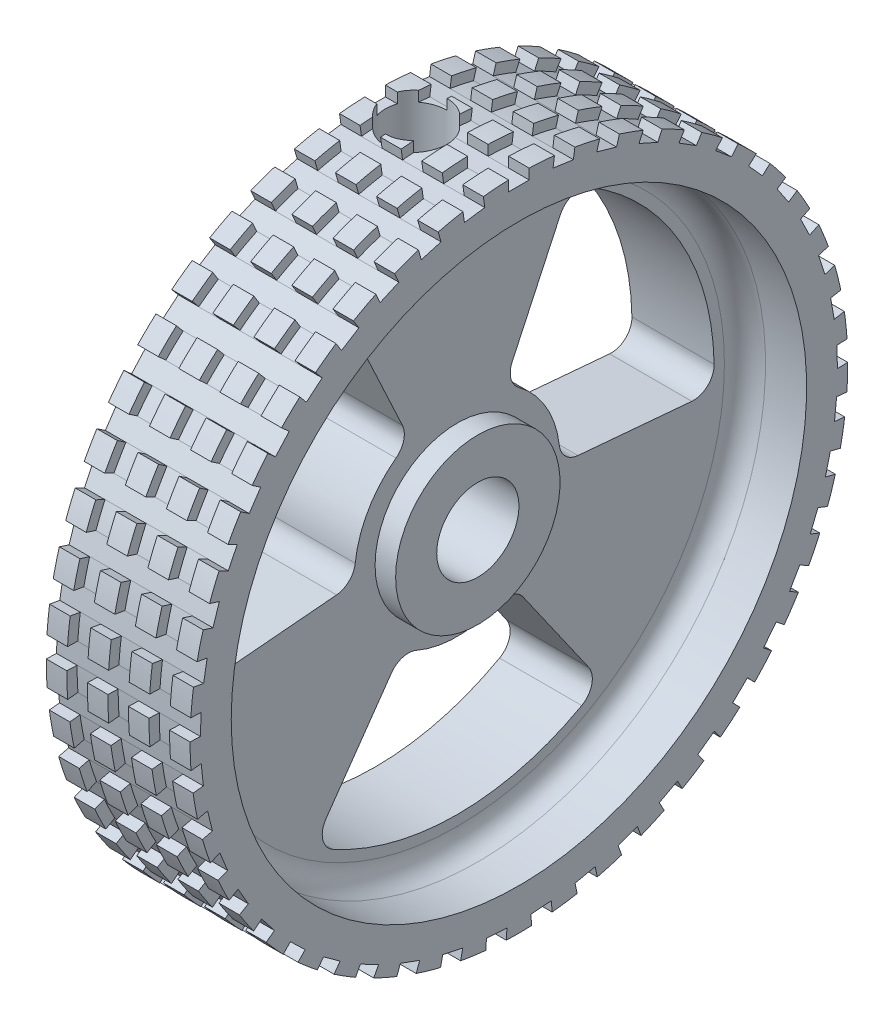
SolidWorks part; units mm, degrees
ref_plane "Front" through (0, 0, 0) normal (0, 0, 1) x (1, 0, 0)
ref_plane "Top" through (0, 0, 0) normal (0, 1, 0) x (1, 0, 0)
ref_plane "Right" through (0, 0, 0) normal (1, 0, 0) x (0, 0, -1)
sketch "Sketch1" plane through (0, 0, 0) normal (0, 0, 1) x (1, 0, 0)
  line L0 (0, 0) -> (0, 24.7296) construction
  line L1 (0, 0) -> (11.8667, 0) construction
  line L2 (0, 2) -> (5, 2)
  line L3 (5, 2) -> (5, 4)
  line L4 (5, 4) -> (4, 4)
  line L5 (4, 4) -> (4, 14)
  line L6 (4, 14) -> (7, 14)
  line L7 (7, 14) -> (7, 16)
  line L8 (7, 16) -> (0, 16)
  line L9 (0, 16) -> (0, 2)
  dimension "D1" = 4
  dimension "D2" = 32
  dimension "D3" = 8
  dimension "D4" = 28
  dimension "D5" = 4
  dimension "D6" = 7
  dimension "D7" = 5
revolve "Revolve1" add sketch "Sketch1" angle 360 about L1
sketch "Sketch2" plane through (0, 0, 0) normal (0, 0, 1) x (1, 0, 0)
  line L0 (2, 0) -> (2, 15.8033) construction
  line L2 (2, 16) -> (3.5, 16)
  line L3 (7, 16) -> (0, 16) construction
  line L4 (3.5, 16) -> (3.5, 11.5)
  line L6 (3.5, 11.5) -> (2.9, 11.5)
  line L7 (2.9, 11.5) -> (2.9, 0)
  line L8 (0, 0) -> (6.9041, 0) construction
  line L9 (2, 0) -> (2, 16)
  line L10 (0, 16) -> (0, -16) construction
  line L11 (2, 0) -> (2.9, 0)
  dimension "D1" = 3
  dimension "D2" = 1.8
  dimension "D3" = 2
  dimension "D4" = 4.5
revolve "Cut-Revolve3" cut sketch "Sketch2" angle 360 about L0
sketch "Sketch3" plane through (4, 0, 0) normal (1, 0, 0) x (0, 0, -1)
  line L0 (-2.6967, -4.2104) -> (-7, -10.3562)
  line L1 (2.6967, -4.2104) -> (7, -10.3562)
  line L3 (0, 0) -> (0, -11.8419) construction
  arc A0 (-7, -10.3562) -> (7, -10.3562) centre (0, 0) ccw
  arc A1 (-2.6967, -4.2104) -> (2.6967, -4.2104) centre (0, 0) ccw
  dimension "D1" = 12.5
  dimension "D3" = 5
  dimension "D2" = 70
  dimension "D4" = 14
extrude "Cut-Extrude3" cut sketch "Sketch3" against normal through all contours A0 L1 A1 L0
fillet "Fillet1" radius 1 4 edges at (2, -10.3562, 7) (2, -4.2104, 2.6967) (2, -4.2104, -2.6967) (2, -10.3562, -7)
pattern_circular "CirPattern1" count 3 over 360 about axis through (0, 0, 0) along (-1, 0, 0) of "Cut-Extrude3", "Fillet1"
fillet "Fillet2" radius 1 1 edges at (4, 0, 14)
sketch "Sketch6" plane through (0, 0, 0) normal (0, 0, 1) x (1, 0, 0)
  line L1 (6, 16) -> (5, 16)
  line L2 (6, 16) -> (6, 15.5)
  line L3 (6, 15.5) -> (5, 15.5)
  line L4 (5, 16) -> (5, 15.5)
  line L5 (7, -16) -> (7, 16) construction
  line L6 (0, 0) -> (7.741, 0) construction
  line L7 (7, 16) -> (3.5, 16) construction
  dimension "D1" = 1
  dimension "D2" = 1
  dimension "D3" = 0.5
revolve "Cut-Revolve4" cut sketch "Sketch6" angle 360 about L6
sketch "Sketch5" plane through (7, 0, 0) normal (1, 0, 0) x (0, 0, -1)
  line L0 (-0.5, 15.9922) -> (-0.5, 15.4922)
  line L1 (-0.5, 15.4922) -> (0.5, 15.4922)
  line L2 (0.5, 15.4922) -> (0.5, 15.9922)
  line L3 (0, 0) -> (0, 24.3586) construction
  circle A0 centre (0, 0) radius 16 construction
  arc A1 (0.5, 15.9922) -> (-0.5, 15.9922) centre (0, 0) ccw
  dimension "D1" = 1
  dimension "D2" = 0.5
extrude "Cut-Extrude4" cut sketch "Sketch5" against normal through all
pattern_circular "CirPattern2" count 45 over 360 about axis through (0, 0, 0) along (-1, 0, 0) of "Cut-Extrude4"
pattern_linear "LPattern1" count 3 spacing 2 along (-1, 0, 0) of "Cut-Revolve4"
